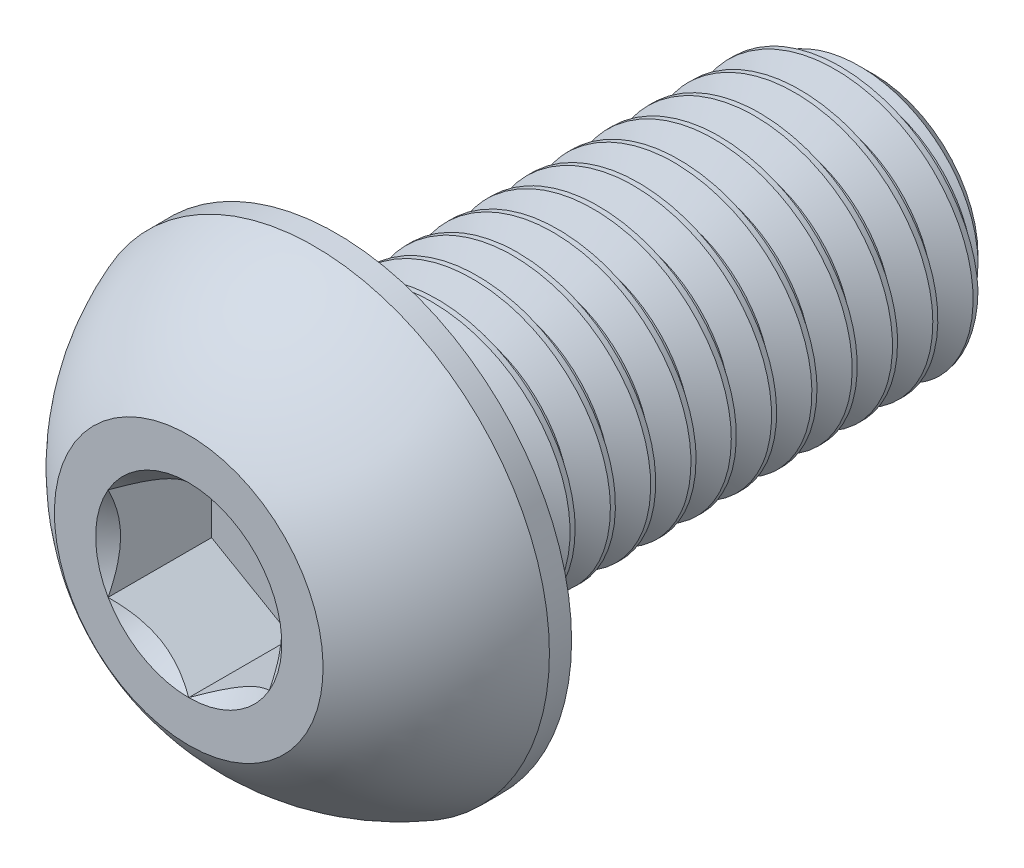
SolidWorks part; units mm, degrees
material "AISI 1020 Steel, Cold Rolled"
ref_plane "Front" through (0, 0, 0) normal (0, 0, 1) x (1, 0, 0)
ref_plane "Top" through (0, 0, 0) normal (0, 1, 0) x (1, 0, 0)
ref_plane "Right" through (0, 0, 0) normal (1, 0, 0) x (0, 0, -1)
sketch "Sketch1" plane through (0, 0, 0) normal (1, 0, 0) x (0, 0, -1)
  line L2 (5.5, 5) -> (25.5, 5)
  line L3 (25.5, 5) -> (25.5, 0)
  line L4 (25.5, 0) -> (5.5, 0)
  line L6 (4.675, 8.75) -> (5.5, 8.75) construction
  line L7 (25.5, 5) -> (25.5, -5) construction
  line L8 (0, 0) -> (5.5, 0) construction
  line L9 (5.5, 8.75) -> (5.5, -8.75) construction
  line L11 (5.5, 5) -> (5.5, 0)
  line L13 (0, 3) -> (0, -3) construction
  line L14 (0, 3) -> (0, 5) construction
  line L15 (25.4063, 5.1624) -> (26.1563, 3.8633) construction
  line L16 (26.1563, 3.8633) -> (26.9063, 5.1624) construction
  line L17 (26.9063, 5.1624) -> (25.4063, 5.1624) construction
  line L18 (25.5, 5) -> (26.8125, 5) construction
  line L19 (26.1563, 5.1624) -> (26.1563, 5) construction
  line L20 (26.1563, 5) -> (26.1563, 4.0257) construction
  line L21 (26.1563, 4.0257) -> (26.1563, 3.8633) construction
  line L22 (26.0625, 4.0257) -> (26.25, 4.0257)
  line L23 (25.4531, 5.0812) -> (26.8594, 5.0812)
  line L24 (26.25, 4.0257) -> (26.8594, 5.0812)
  line L25 (26.0625, 4.0257) -> (25.4531, 5.0812)
  line L26 (24.375, 5) -> (25.5, 3.875)
  arc A3 (0, 5) -> (4.675, 8.75) centre (7.8522, 0) cw construction
  point P29 (26.1563, 5.0812)
  point P30 (21.75, -5)
  dimension "D1" = 0.825
  dimension "Pitch" = 1.5
  dimension "D3" = 0.1875
  dimension "D2" = 1.125
  dimension "D4" = 45
  dimension "D5" = 3.75
sketch "Sketch10" plane through (0, 0, 0) normal (1, 0, 0) x (0, 0, -1)
  line L0 (24.375, 5) -> (25.5, 3.875) construction
  line L1 (24.375, 5) -> (25.5, 3.875)
  line L4 (25.5, 5) -> (5.5, 5)
  line L5 (25.5, 0) -> (25.5, 5)
  line L6 (5.5, 0) -> (25.5, 0)
  line L7 (5.5, 5) -> (5.5, 0)
  line L8 (24.375, 5) -> (5.5, 5)
  line L9 (25.5, 0) -> (25.5, 3.875)
  line L10 (5.5, 0) -> (25.5, 0)
  line L11 (5.5, 5) -> (5.5, 0)
  dimension "D1" = 0
revolve "Revolve3" add sketch "Sketch10" angle 360 about L8
sketch "Sketch7" plane through (0, 0, 0) normal (1, 0, 0) x (0, 0, -1)
  line L6 (4.675, 8.75) -> (5.5, 8.75) construction
  line L8 (0, 0) -> (5.5, 0) construction
  line L11 (5.5, 8.75) -> (5.5, -8.75) construction
  line L12 (4.675, 8.75) -> (5.5, 8.75)
  line L13 (0, 0) -> (5.5, 0)
  line L14 (0, 3) -> (0, -3) construction
  line L15 (5.5, 8.75) -> (5.5, 0)
  line L16 (0, 5) -> (0, 0)
  arc A2 (4.675, 8.75) -> (0, 5) centre (7.8522, 0) ccw construction
  arc A3 (4.675, 8.75) -> (0, 5) centre (7.8522, 0) ccw
revolve "Revolve2" add sketch "Sketch7" angle 360 mid plane about L13
sketch "Sketch5" plane through (0, 0, 0) normal (0, 0, 1) x (1, 0, 0)
  line L1 (3, -1.7321) -> (3, 1.7321)
  line L2 (3, 1.7321) -> (0, 3.4641)
  line L3 (0, 3.4641) -> (-3, 1.7321)
  line L4 (-3, 1.7321) -> (-3, -1.7321)
  line L5 (-3, -1.7321) -> (0, -3.4641)
  line L6 (0, -3.4641) -> (3, -1.7321)
  circle A0 centre (0, 0) radius 3 construction
extrude "Cut-Extrude2" cut sketch "Sketch5" against normal blind 3.85
sketch "Sketch6" plane through (0, 0, 0) normal (0, 0, 1) x (1, 0, 0)
  circle A0 centre (0, 0) radius 3.4641
extrude "Cut-Extrude3" cut sketch "Sketch6" against normal blind 3.85 draft 45
sketch "Sketch9" plane through (0, 0, -5.5) normal (0, 0, -1) x (-1, 0, 0)
  circle A0 centre (0, 0) radius 5 construction
  circle A4 centre (0, 0) radius 5
split "Split1" bodies to split 113 resulting bodies 123 124 split by face at (8.75, 0, -5.5)
sketch "Sketch11" plane through (0, 0, -25.5) normal (0, 0, -1) x (-1, 0, 0)
  circle A0 centre (0, 0) radius 5 construction
  circle A1 centre (0, 0) radius 5
curve "Helix/Spiral1" pitch 1.5 height 25.5 radius 5 centre (0, 0, -25.5) axis (0, 0, 1) start towards (0, 1, 0)
sketch "Sketch12" plane through (0, 0, 0) normal (1, 0, 0) x (0, 0, -1)
  line L0 (26.0625, 4.0257) -> (26.25, 4.0257) construction
  line L1 (26.25, 4.0257) -> (26.8594, 5.0812) construction
  line L2 (25.4531, 5.0812) -> (26.8594, 5.0812) construction
  line L3 (26.0625, 4.0257) -> (25.4531, 5.0812) construction
  line L4 (26.0625, 4.0257) -> (26.25, 4.0257)
  line L5 (26.25, 4.0257) -> (26.8594, 5.0812)
  line L6 (25.4531, 5.0812) -> (26.8594, 5.0812)
  line L7 (26.0625, 4.0257) -> (25.4531, 5.0812)
sweep "Cut-Sweep2" cut profiles "Sketch12" path "Helix/Spiral1" align with end faces yes
extrude "Boss-Extrude1" add sketch "Sketch9" along normal blind 10 draft 45
equation "\"D1@Cut-Extrude2\" = \"Head Ht@Sketch1\" * .7"
equation "\"D1@Sketch1\" = \"Head Ht@Sketch1\" * .15"
equation "\"D1@Cut-Extrude3\" = \"D1@Cut-Extrude2\""
equation "\"D3@Sketch1\" = \"Pitch@Sketch1\" / 8"
equation "\"D2@Sketch1\"=\"Pitch@Sketch1\"*0.75"
equation "\"D3@Helix/Spiral1\" = \"Lg@Sketch1\" + \"Head Ht@Sketch1\""
equation "\"D4@Helix/Spiral1\"=\"pitch@sketch1\""
equation "\"D5@Sketch1\"=\"Pitch@Sketch1\"*2.5"
